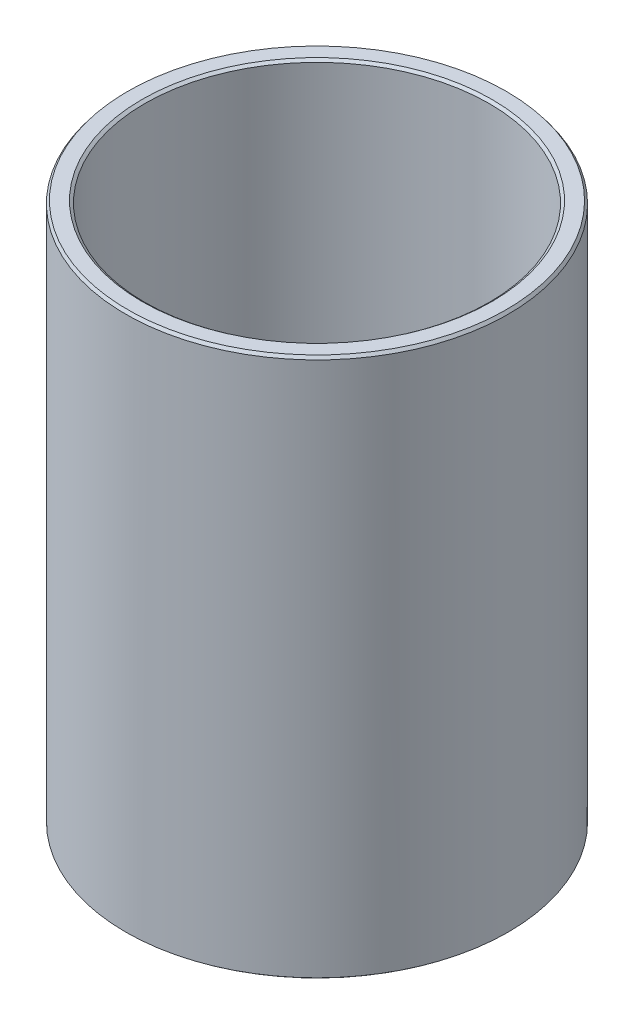
SolidWorks part; units mm, degrees
ref_plane "Front Plane" through (0, 0, 0) normal (0, 0, 1) x (1, 0, 0)
ref_plane "Top Plane" through (0, 0, 0) normal (0, 1, 0) x (1, 0, 0)
ref_plane "Right Plane" through (0, 0, 0) normal (1, 0, 0) x (0, 0, -1)
sketch "Sketch1" plane through (0, 0, 0) normal (0, 1, 0) x (1, 0, 0)
  circle A0 centre (0, 0) radius 55
  dimension "SLEEVE_OD" = 110
extrude "Boss-Extrude1" add sketch "Sketch1" along normal blind 155.241
sketch "Sketch2" plane through (0, 0, 0) normal (0, 1, 0) x (1, 0, 0)
  circle A0 centre (0, 0) radius 49.5029
  dimension "BORE_D" = 99.0057
extrude "Cut-Extrude1" cut sketch "Sketch2" along normal through all
chamfer "Chamfer1" distance 0.8071 angle 37.222 4 edges at (0, 155.241, 49.5029) (0, 0, 49.5029) (0, 0, 55) (0, 155.241, 55) first distance on face at (0, 155.241, 49.5029) first distance on face at (0, 0, 49.5029) first distance on face at (0, 155.241, 55)
